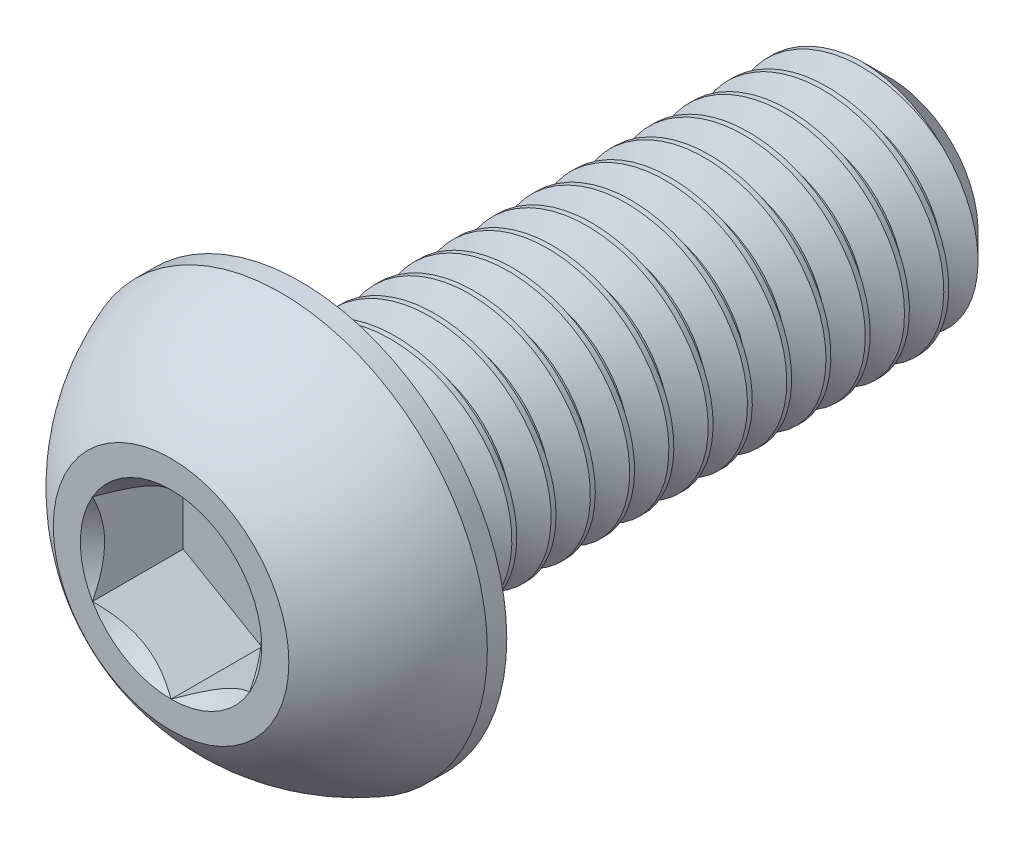
SolidWorks part; units mm, degrees
note: '?' marks a value the reader was unsure of.
ref_plane "Front" through (0, 0, 0) normal (0, 0, 1) x (1, 0, 0)
ref_plane "Top" through (0, 0, 0) normal (0, 1, 0) x (1, 0, 0)
ref_plane "Right" through (0, 0, 0) normal (1, 0, 0) x (0, 0, -1)
sketch "Sketch1" plane through (0, 0, 0) normal (1, 0, 0) x (0, 0, -1)
  line L2 (3.3, 3) -> (18.3, 3)
  line L3 (18.3, 3) -> (18.3, 0)
  line L4 (18.3, 0) -> (3.3, 0)
  line L6 (2.805, 5.25) -> (3.3, 5.25) construction
  line L7 (18.3, 3) -> (18.3, -3) construction
  line L8 (0, 0) -> (3.3, 0) construction
  line L9 (3.3, 5.25) -> (3.3, -5.25) construction
  line L11 (3.3, 3) -> (3.3, 0)
  line L13 (0, 2) -> (0, -2) construction
  line L14 (0, 2) -> (0, 3) construction
  arc A3 (0, 3) -> (2.805, 5.25) centre (4.7113, 0) cw construction
  dimension "D1" = 0.495
revolve "Revolve1" add sketch "Sketch1" angle 360 mid plane about L4
sketch "Sketch3" plane through (0, 0, -18.3) normal (0, 0, -1) x (-1, 0, 0)
  circle A0 centre (0, 0) radius 3
curve "Helix/Spiral1" pitch 1 height 16 turns 16
chamfer "Chamfer1" distance 0.75 angle 45 1 edges at (-3, 0, -18.3)
sketch "Sketch7" plane through (0, 0, 0) normal (1, 0, 0) x (0, 0, -1)
  line L6 (2.805, 5.25) -> (3.3, 5.25) construction
  line L8 (0, 0) -> (3.3, 0) construction
  line L11 (3.3, 5.25) -> (3.3, -5.25) construction
  line L12 (2.805, 5.25) -> (3.3, 5.25)
  line L13 (0, 0) -> (3.3, 0)
  line L14 (0, 2) -> (0, -2) construction
  line L15 (3.3, 5.25) -> (3.3, 0)
  line L16 (0, 3) -> (0, 0)
  arc A2 (2.805, 5.25) -> (0, 3) centre (4.7113, 0) ccw construction
  arc A3 (2.805, 5.25) -> (0, 3) centre (4.7113, 0) ccw
revolve "Revolve2" add sketch "Sketch7" angle 360 mid plane about L13
sketch "Sketch5" plane through (0, 0, 0) normal (0, 0, 1) x (1, 0, 0)
  line L1 (2, -1.1547) -> (2, 1.1547)
  line L2 (2, 1.1547) -> (0, 2.3094)
  line L3 (0, 2.3094) -> (-2, 1.1547)
  line L4 (-2, 1.1547) -> (-2, -1.1547)
  line L5 (-2, -1.1547) -> (0, -2.3094)
  line L6 (0, -2.3094) -> (2, -1.1547)
  circle A0 centre (0, 0) radius 2 construction
extrude "Cut-Extrude2" cut sketch "Sketch5" against normal blind 2.31
sketch "Sketch6" plane through (0, 0, 0) normal (0, 0, 1) x (1, 0, 0)
  circle A0 centre (0, 0) radius 2.3094
extrude "Cut-Extrude3" cut sketch "Sketch6" against normal blind 2.31 draft 45
sketch "Sketch2" plane through (0, 0, 0) normal (1, 0, 0) x (0, 0, -1)
  line L0 (17.55, 3) -> (18.425, 3)
  line L1 (18.425, 3) -> (18.05, 2.3505)
  line L2 (18.05, 2.3505) -> (17.925, 2.3505)
  line L3 (17.925, 2.3505) -> (17.55, 3)
  line L4 (17.7375, 2.6752) -> (18.2375, 2.6752) construction
  dimension "D1" = 60
  dimension "D2" = 0.125
  dimension "D3" = 0.5
sweep "Cut-Sweep1" cut profiles "Sketch2" path "Helix/Spiral1"
sketch "Sketch10" plane through (0, 0, 0) normal (1, 0, 0) x (0, 0, -1)
  line L0 (18.3, 3) -> (18.3, -3) construction
  point P0 (16.8, -3)
  dimension "D1" = 1.5
ref_axis "Center Axis 1" through (0, 0, -8.1113) along (0, 0, 1)?
ref_plane "Contact Plane 1" through (0, 0, -3.3) normal (0, 0, -1) x (-1, 0, 0)
ref_plane "Contact Plane 2" through (0, 0, 0) normal (0, 0, 1) x (1, 0, 0)
equation "\"D3@Helix/Spiral1\" = \"Lg@Sketch1\" + \"D4@Helix/Spiral1\""
equation "\"D2@Sketch2\" = \"D4@Helix/Spiral1\" * .125"
equation "\"D3@Sketch2\" = \"D4@Helix/Spiral1\" * .5"
equation "\"D1@Chamfer1\" = \"D4@Helix/Spiral1\" * .75"
equation "\"D1@Cut-Extrude2\" = \"Head Ht@Sketch1\" * .7"
equation "\"D1@Sketch1\" = \"Head Ht@Sketch1\" * .15"
equation "\"D1@Sketch10\" = \"D4@Helix/Spiral1\" * 1.5"
equation "\"D1@Cut-Extrude3\" = \"D1@Cut-Extrude2\""
